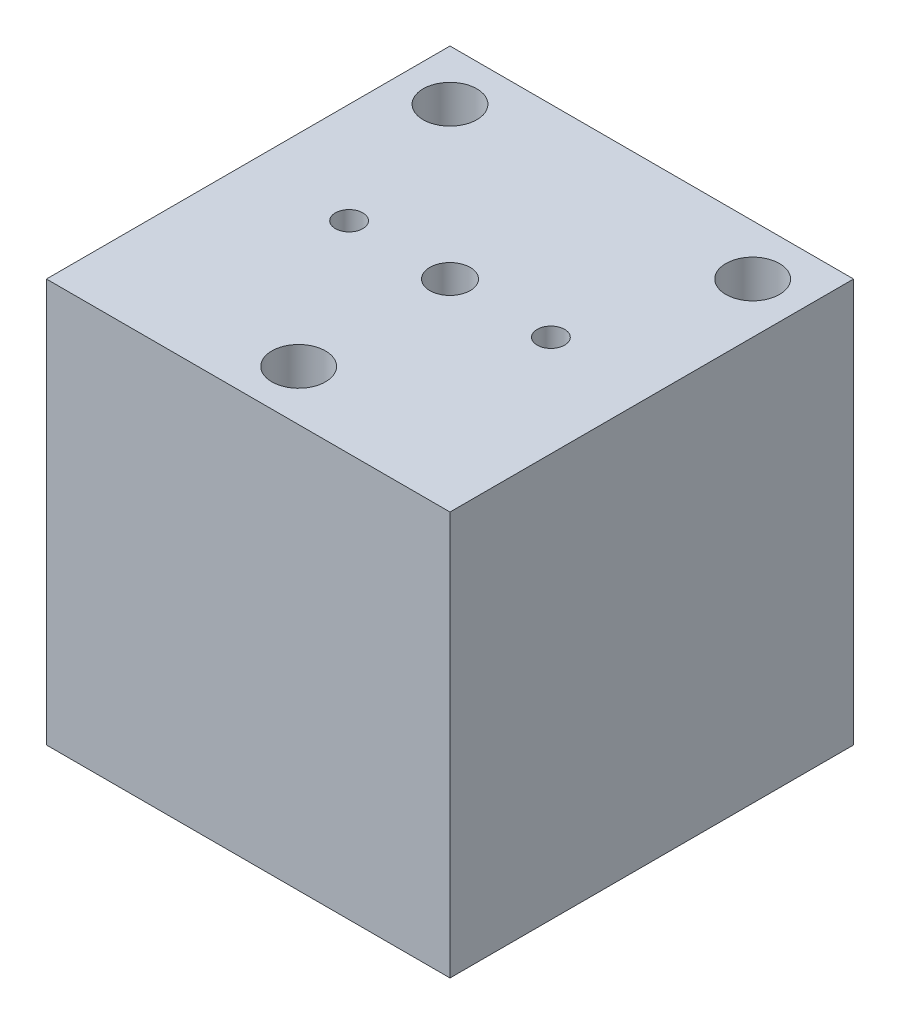
SolidWorks part; units mm, degrees
ref_plane "Front Plane" through (0, 0, 0) normal (0, 0, 1) x (1, 0, 0)
ref_plane "Top Plane" through (0, 0, 0) normal (0, 1, 0) x (1, 0, 0)
ref_plane "Right Plane" through (0, 0, 0) normal (1, 0, 0) x (0, 0, -1)
sketch "Sketch1" plane through (0, 0, 0) normal (0, 1, 0) x (1, 0, 0)
  line L1 (-25.4, 25.4) -> (25.4, 25.4)
  line L2 (-25.4, 25.4) -> (-25.4, -25.4)
  line L3 (-25.4, -25.4) -> (25.4, -25.4)
  line L4 (25.4, 25.4) -> (25.4, -25.4)
  dimension "D1" = 50.8
  dimension "D2" = 50.8
  dimension "D3" = 25.4
  dimension "D4" = 25.4
extrude "Boss-Extrude1" add sketch "Sketch1" along normal blind 50.8
hole_wizard "1/4 Clearance Hole1" positions "Sketch3" profile "Sketch2" hole size "1/4" standard "ANSI Inch" end condition through all
sketch "Sketch3" plane through (0, 50.8, 0) normal (0, 1, 0) x (1, 0, 0)
  point P0 (-19.05, 19.05)
  point P2 (19.05, 19.05)
  point P4 (0, -19.05)
sketch "Sketch2" plane through (-19.05, 50.8, -19.05) normal (1, 0, 0) x (0, 0, 1)
  line L0 (0, 0) -> (0, 50.8)
  line L1 (0, 50.8) -> (3.3782, 50.8)
  line L2 (3.3782, 50.8) -> (3.3782, 0)
  line L5 (3.3782, 0) -> (0, 0)
  line L11 (0, -6.35) -> (0, 107.95) construction
  dimension "Thru Hole Dia." = 6.7564
  dimension "Thru Hole Depth" = 50.8
sketch "Sketch4" plane through (0, 50.8, 0) normal (0, 1, 0) x (1, 0, 0)
  circle A0 centre (0, 0) radius 2.54
extrude "Cut-Extrude1" cut sketch "Sketch4" against normal through all
hole_wizard "Tap Drill for #8-32 Tap1" positions "Sketch6" profile "Sketch5" hole size "#8-32" standard "ANSI Inch"
sketch "Sketch6" plane through (0, 50.8, 0) normal (0, 1, 0) x (1, 0, 0)
  point P0 (-12.7, 0)
  point P2 (12.7, 0)
sketch "Sketch5" plane through (-12.7, 50.8, 0) normal (1, 0, 0) x (0, 0, 1)
  line L0 (0, 0) -> (0, 13.7378)
  line L1 (0, 13.7378) -> (1.7272, 12.7)
  line L2 (1.7272, 12.7) -> (1.7272, 0)
  line L5 (1.7272, 0) -> (0, 0)
  line L10 (0, 13.7378) -> (-1.7272, 12.7) construction
  line L11 (0, -6.35) -> (0, 107.95) construction
  dimension "Hole Dia." = 3.4544
  dimension "Hole Depth" = 12.7
  dimension "Drill Angle" = 118
